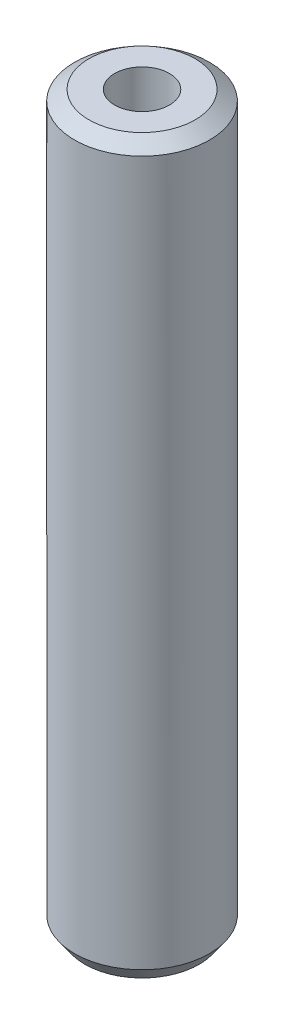
SolidWorks part; units mm, degrees
ref_plane "Front Plane" through (0, 0, 0) normal (0, 0, 1) x (1, 0, 0)
ref_plane "Top Plane" through (0, 0, 0) normal (0, 1, 0) x (1, 0, 0)
ref_plane "Right Plane" through (0, 0, 0) normal (1, 0, 0) x (0, 0, -1)
sketch "Sketch1" plane through (0, 0, 0) normal (0, 1, 0) x (1, 0, 0)
  circle A0 centre (0, 0) radius 30
  dimension "SHAFT_OD" = 60
extrude "Boss-Extrude1" add sketch "Sketch1" along normal blind 324.3453
sketch "Sketch2" plane through (0, 0, 0) normal (0, 1, 0) x (1, 0, 0)
  circle A0 centre (0, 0) radius 12.1882
  dimension "BORE_D" = 24.3765
extrude "Cut-Extrude1" cut sketch "Sketch2" along normal through all
chamfer "Chamfer1" distance 4.5652 angle 54.526 2 edges at (0, 324.3453, 30) (0, 0, 30) first distance on face at (0, 324.3453, 30) first distance on face at (0, 0, 12.1882)
